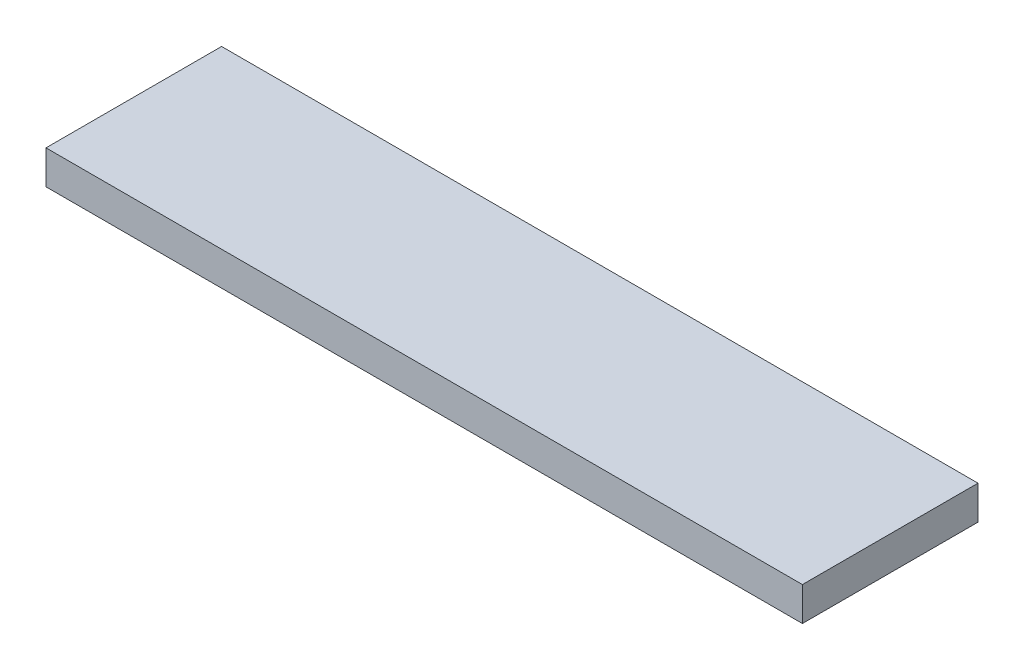
SolidWorks part; units mm, degrees
ref_plane "前视基准面" through (0, 0, 0) normal (0, 0, 1) x (1, 0, 0)
ref_plane "上视基准面" through (0, 0, 0) normal (0, 1, 0) x (1, 0, 0)
ref_plane "右视基准面" through (0, 0, 0) normal (1, 0, 0) x (0, 0, -1)
sketch "草图1" plane through (0, 0, 0) normal (0, 1, 0) x (1, 0, 0)
  line L1 (0, 0) -> (224, 0)
  line L2 (0, 0) -> (0, -52)
  line L3 (0, -52) -> (224, -52)
  line L4 (224, 0) -> (224, -52)
  dimension "D1" = 224
  dimension "D2" = 52
extrude "凸台-拉伸1" add sketch "草图1" along normal blind 10
